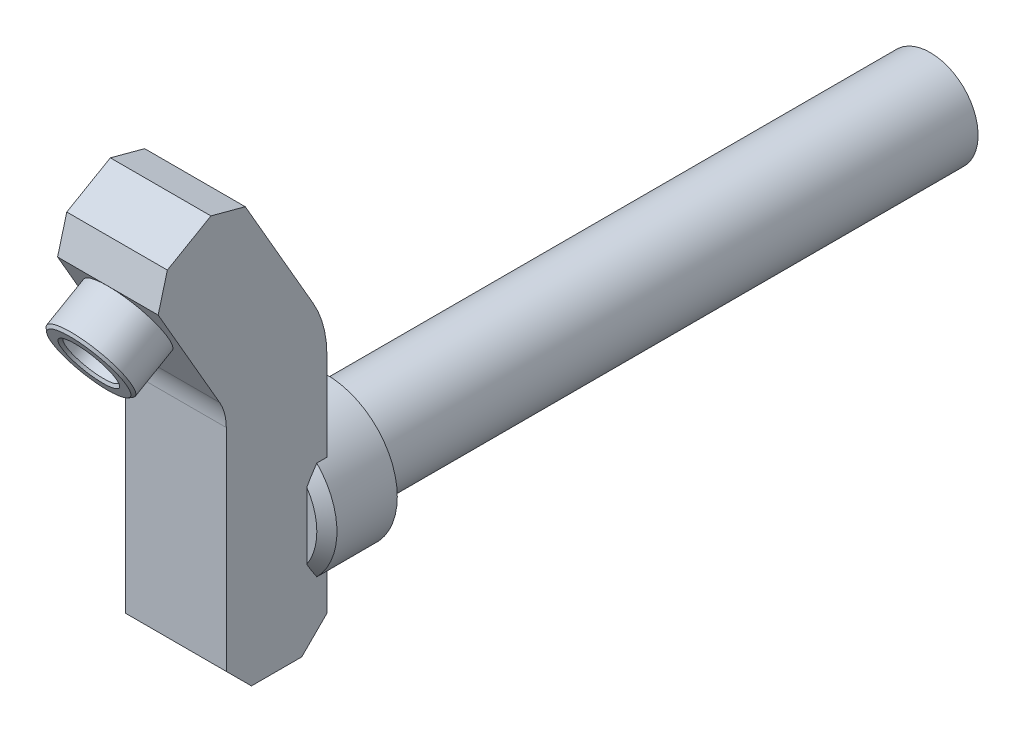
SolidWorks part; units mm, degrees
ref_plane "Front Plane" through (0, 0, 0) normal (0, 0, 1) x (1, 0, 0)
ref_plane "Top Plane" through (0, 0, 0) normal (0, 1, 0) x (1, 0, 0)
ref_plane "Right Plane" through (0, 0, 0) normal (1, 0, 0) x (0, 0, -1)
sketch "Sketch1" plane through (0, 0, 0) normal (0, 0, 1) x (1, 0, 0)
  circle A0 centre (0, 0) radius 9.5
  dimension "D1" = 19
extrude "Boss-Extrude1" add sketch "Sketch1" along normal blind 120
sketch "Sketch2" plane through (0, 0, 0) normal (0, 0, -1) x (-1, 0, 0)
  line L0 (0, 0) -> (9.5, 0)
  circle A0 centre (0, 0) radius 9.5 construction
  circle A1 centre (0, 0) radius 9.5
  arc A2 (9.2895, 1.9889) -> (9.2895, -1.9889) centre (9.5, 0) ccw
  point P6 (7.5, 0)
  point P7 (0, 0)
  circle M3 centre (0, 0) radius 9.5
  dimension "D1" = 7.5
extrude "Cut-Extrude1" cut sketch "Sketch2" against normal blind 40 contours L0 A2 M3 | A2 L0 M3 region at (-8.6144, 0.8184, 0) region at (-8.6144, -0.8184, 0)
sketch "Sketch3" plane through (0, 0, 120) normal (0, 0, 1) x (1, 0, 0)
  circle A0 centre (0, 0) radius 9.5 construction
  circle A1 centre (0, 0) radius 9.5
  circle A2 centre (0, 0) radius 14
  circle M3 centre (0, 0) radius 9.5
  dimension "D1" = 28
extrude "Boss-Extrude2" add sketch "Sketch3" along normal blind 14 separate body contours M3 | A2 M3 region at (0, 0, 120) region at (-13.604, 0, 120)
chamfer "Chamfer1" distance 2 angle 45 1 edges at (14, 0, 134)
sketch "Sketch4" plane through (0, 0, 0) normal (1, 0, 0) x (0, 0, -1)
  line L0 (-134, 12) -> (-134, -12) construction
  line L1 (-134, 12) -> (-134, -12)
  line L2 (-134, 0) -> (-150, 0) construction
  line L3 (-150, -22.0882) -> (-130, -22.0882)
  line L4 (-150, -22.0882) -> (-150, 24.9118)
  line L6 (-130, -22.0882) -> (-130, 27.5)
  line L7 (-150, 0) -> (-235.6, 0) construction
  line L8 (-235.6, 0) -> (-86.8361, 85.8889) construction
  line L9 (-120, 14) -> (-132, 14) construction
  line L14 (-151.3397, 29.9118) -> (-166.0526, 55.3952)
  line L15 (-150.3407, 27.5) -> (-130, 27.5) construction
  line L16 (-132.7251, 37.6704) -> (-148.7321, 65.3952)
  line L17 (-166.0526, 55.3952) -> (-148.7321, 65.3952)
  line L18 (-120, 14) -> (-132, 14)
  arc A0 (-151.3397, 29.9118) -> (-150, 24.9118) centre (-160, 24.9118) cw
  arc A1 (-130, 27.5) -> (-132.7251, 37.6704) centre (-150.3407, 27.5) ccw
  point P2 (-134, 0)
  dimension "D7" = 10
  dimension "D8" = 20
  dimension "D1" = 20
  dimension "D2" = 4
  dimension "D3" = 85.6
  dimension "D4" = 30
  dimension "D5" = 13.2
  dimension "D6" = 47
  dimension "D9" = 13.5
extrude "Boss-Extrude3" add sketch "Sketch4" along normal mid plane 20 contours L6 A1 L16 L17 L14 A0 L4 L3 region at (0, 20.5913, 143.2942)
sketch "Sketch5" plane through (0, -58.0541, 100.5526) normal (0, -0.5, 0.866) x (1, 0, 0)
  line L0 (10, 131) -> (-10, 131) construction
  line L1 (10, 131) -> (-10, 131) construction
  line L2 (0, 131) -> (0, 118) construction
  circle A0 centre (0, 118) radius 8
  dimension "D1" = 16
  dimension "D2" = 13
extrude "Boss-Extrude4" add sketch "Sketch5" along normal blind 9
sketch "Sketch6" plane through (0, -62.5541, 108.3468) normal (0, -0.5, 0.866) x (1, 0, 0)
  circle A0 centre (0, 118) radius 8 construction
  circle A1 centre (0, 118) radius 8
  circle A2 centre (0, 118) radius 5
  dimension "D1" = 10
extrude "Cut-Extrude2" cut sketch "Sketch6" against normal through all contours A2 region at (0, 39.6369, 167.3468)
chamfer "Chamfer2" distance 0.5 angle 45 2 edges at (0, 49.8068, 139.7321) (0, 35.3068, 164.8468)
chamfer "Chamfer3" distance 0.5 angle 45 1 edges at (0, 32.7087, 163.3468)
chamfer "Chamfer4" distance 5 angle 45 4 edges at (0, 65.3952, 148.7321) (0, 55.3952, 166.0526) (0, -22.0882, 130) (0, -22.0882, 150)
